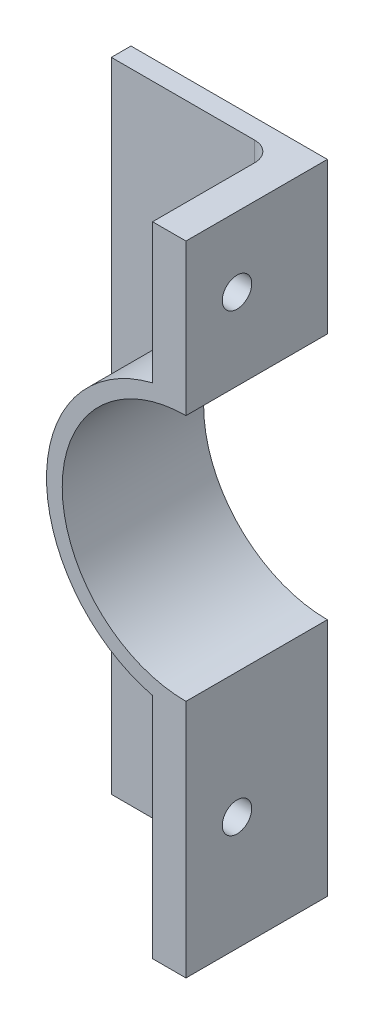
SolidWorks part; units mm, degrees
ref_plane "Front Plane" through (0, 0, 0) normal (0, 0, 1) x (1, 0, 0)
ref_plane "Top Plane" through (0, 0, 0) normal (0, 1, 0) x (1, 0, 0)
ref_plane "Right Plane" through (0, 0, 0) normal (1, 0, 0) x (0, 0, -1)
sketch "Sketch3" plane through (0, 0, 0) normal (0, 0, 1) x (1, 0, 0)
  line L0 (0, 0) -> (0, 82.55)
  line L1 (0, 82.55) -> (50.8, 82.55)
  line L2 (50.8, 82.55) -> (50.8, 0)
  line L3 (50.8, 0) -> (0, 0)
  line L4 (25.4, 82.55) -> (25.4, 0)
  line L6 (21.082, 82.55) -> (21.082, 64.4994)
  line L7 (21.082, 0) -> (21.082, 29.4806)
  line L8 (29.718, 82.55) -> (29.718, 64.4994)
  line L9 (29.718, 0) -> (29.718, 29.4806)
  circle A1 centre (25.4, 46.99) radius 16.002
  arc A2 (29.718, 29.4806) -> (29.718, 64.4994) centre (25.4, 46.99) ccw
  arc A3 (21.082, 64.4994) -> (21.082, 29.4806) centre (25.4, 46.99) ccw
extrude "Boss-Extrude2" add sketch "Sketch3" along normal blind 2.54 contours A3 L6 L1 L0 L3 L7 region at (0.852, 41.275, 0)
extrude "Boss-Extrude3" add sketch "Sketch3<5>" along normal blind 18.288 contours L6 A3 L7 L3 L4 A1 L1 region at (21.927, 14.7403, 0)
sketch "Sketch3<5>" plane through (0, 0, 0) normal (0, 0, 1) x (1, 0, 0) same geometry as "Sketch3"
fillet "Fillet1" radius 2.54 3 edges at (21.082, 73.5247, 2.54) (7.366, 46.99, 2.54) (21.082, 14.7403, 2.54)
sketch "Sketch4" plane through (0, 0, 0) normal (1, 0, 0) x (0, 0, -1)
  circle A1 centre (-11.684, 14.7403) radius 1.905
  circle A2 centre (-11.684, 73.5247) radius 1.905
extrude "Cut-Extrude1" cut sketch "Sketch4" against normal through all and the other way through all
